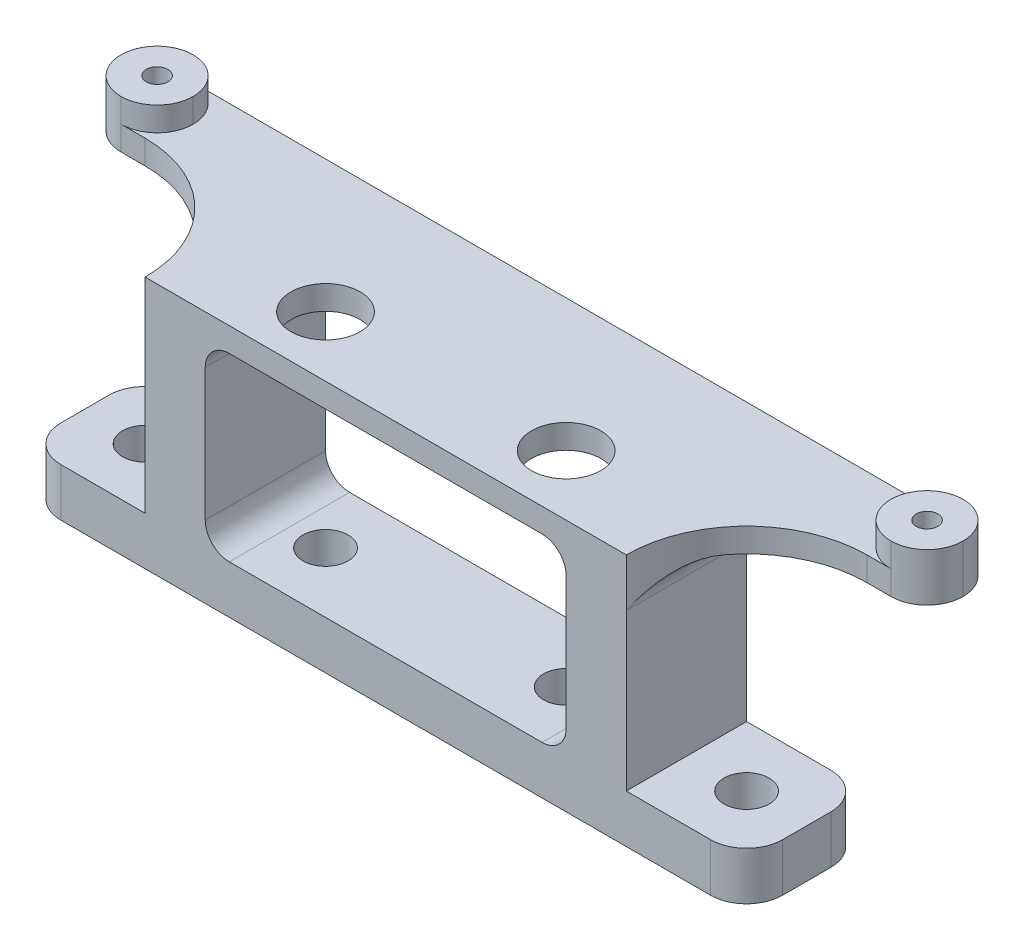
SolidWorks part; units mm, degrees
ref_plane "Front Plane" through (0, 0, 0) normal (0, 0, 1) x (1, 0, 0)
ref_plane "Top Plane" through (0, 0, 0) normal (0, 1, 0) x (1, 0, 0)
ref_plane "Right Plane" through (0, 0, 0) normal (1, 0, 0) x (0, 0, -1)
sketch "Sketch1" plane through (0, 0, 0) normal (0, 1, 0) x (1, 0, 0)
  line L1 (-30, -5) -> (30, -5)
  line L2 (-30, -5) -> (-30, 5)
  line L3 (-30, 5) -> (30, 5)
  line L4 (30, -5) -> (30, 5)
  line L5 (-30, -5) -> (30, 5) construction
  line L6 (-30, 5) -> (30, -5) construction
  point P0 (0, 0)
  dimension "D1" = 60
  dimension "D2" = 10
extrude "Boss-Extrude1" add sketch "Sketch1" along normal blind 4 contours L2 L3 L4 L1
sketch "Sketch2" plane through (0, 4, 0) normal (0, 1, 0) x (1, 0, 0)
  line L0 (0, 0) -> (50000, 0) construction
  line L1 (0, 0) -> (0, 50000) construction
  circle A0 centre (-25, 0) radius 1.875
  circle A1 centre (-10, 0) radius 1.875
  circle A2 centre (10, 0) radius 1.875
  circle A3 centre (25, 0) radius 1.875
  dimension "D5" = 3.75
  dimension "D1" = 10
  dimension "D2" = 10
  dimension "D3" = 25
  dimension "D4" = 25
extrude "Cut-Extrude1" cut sketch "Sketch2" against normal through all
sketch "Sketch4" plane through (0, 4, 0) normal (0, 1, 0) x (1, 0, 0)
  line L0 (-23.125, 0) -> (-11.875, 0) construction
  line L1 (11.875, 0) -> (23.125, 0) construction
  line L2 (-30, 5) -> (30, 5) construction
  line L3 (-20, -5) -> (-15, -5)
  line L4 (-20, -5) -> (-20, 5)
  line L5 (-20, 5) -> (-15, 5)
  line L6 (-15, -5) -> (-15, 5)
  line L7 (-20, -5) -> (-15, 5) construction
  line L8 (-20, 5) -> (-15, -5) construction
  line L16 (15, -5) -> (20, -5)
  line L17 (15, -5) -> (15, 5)
  line L18 (15, 5) -> (20, 5)
  line L19 (20, -5) -> (20, 5)
  line L20 (15, -5) -> (20, 5) construction
  line L21 (15, 5) -> (20, -5) construction
  circle A0 centre (-25, 0) radius 1.875 construction
  circle A1 centre (-10, 0) radius 1.875 construction
  circle A2 centre (10, 0) radius 1.875 construction
  circle A3 centre (25, 0) radius 1.875 construction
  point P14 (-17.5, 0)
  point P27 (17.5, 0)
  dimension "D1" = 5
extrude "Boss-Extrude2" add sketch "Sketch4" along normal blind 15
sketch "Sketch5" plane through (0, 19, 0) normal (0, 1, 0) x (1, 0, 0)
  line L0 (-20, -5) -> (20, -5)
  line L1 (20, -5) -> (20, 5)
  line L2 (20, 5) -> (35, 5)
  line L3 (35, 5) -> (35, 11)
  line L4 (35, 11) -> (-35, 11)
  line L5 (-35, 11) -> (-35, 5)
  line L6 (-35, 5) -> (-20, 5)
  line L7 (-20, 5) -> (-20, -5)
  dimension "D1" = 70
  dimension "D2" = 6
extrude "Boss-Extrude3" add sketch "Sketch5" along normal blind 4
sketch "Sketch7" plane through (0, 23, 0) normal (0, 1, 0) x (1, 0, 0)
  line L0 (-20, 5) -> (20, 5) construction
  line L1 (0, 5) -> (0, 11) construction
  line L2 (20, 5) -> (35, 5) construction
  line L3 (-29, 11) -> (29, 11)
  line L4 (-29, 11) -> (-29, 5)
  line L5 (-29, 5) -> (29, 5)
  line L6 (29, 11) -> (29, 5)
  line L7 (-29, 11) -> (29, 5) construction
  line L8 (-29, 5) -> (29, 11) construction
  line L9 (35, 11) -> (-35, 11) construction
  point P7 (0, 8)
  point P14 (0, 11)
  dimension "D1" = 58
sketch "Sketch8" plane through (0, 23, 0) normal (0, 1, 0) x (1, 0, 0)
  line L0 (-32, 8) -> (32, 8) construction
  circle A0 centre (32, 8) radius 0.9
  circle A1 centre (-32, 8) radius 0.9
  point P4 (0, 8)
  dimension "D1" = 1.8
  dimension "D2" = 64
extrude "Cut-Extrude2" cut sketch "Sketch7" against normal blind 2
sketch "Sketch9" plane through (0, 23, 0) normal (0, 1, 0) x (1, 0, 0)
  line L4 (20, 5) -> (-20, 5)
  line L5 (-20, 5) -> (-20, -5)
  line L6 (-20, -5) -> (20, -5)
  line L7 (20, -5) -> (20, 5)
  line L8 (20, 5) -> (-20, 5)
  line L9 (-20, 5) -> (-20, -5)
  line L10 (-20, -5) -> (20, -5)
  line L11 (20, -5) -> (20, 5)
  dimension "D1" = 0
extrude "Cut-Extrude3" cut sketch "Sketch9" against normal up to surface (2 mm away) up to face at (0, 21, -7)
sketch "Sketch10" plane through (0, 21, 0) normal (0, 1, 0) x (1, 0, 0)
  circle A0 centre (10, 0) radius 1.875 construction
  circle A1 centre (-10, 0) radius 1.875 construction
  circle A2 centre (10, 0) radius 1.875 construction
  circle A3 centre (-10, 0) radius 1.875 construction
  circle A4 centre (-10, 0) radius 2.875
  circle A5 centre (10, 0) radius 2.875
  dimension "D1" = 1
extrude "Cut-Extrude5" cut sketch "Sketch10" against normal up to next
fillet "Fillet1" radius 10 2 edges at (20, 20, -5) (-20, 20, -5)
fillet "Fillet2" radius 3 12 edges at (30, 2, -5) (30, 2, 5) (-30, 2, -5) (-30, 2, 5) (-35, 21, -11) (-35, 21, -5) (-29, 22, -11) (29, 22, -11) (35, 21, -11) (35, 21, -5) (-29, 22, -4.9499) (29, 22, -4.9499)
fillet "Fillet3" radius 2 4 edges at (15, 19, 0) (-15, 19, 0) (-15, 4, 0) (15, 4, 0)
extrude "Cut-Extrude4" cut sketch "Sketch8" against normal through all
fillet "Fillet4" radius 2 4 edges at (-16.5, 19, -5) (16.5, 19, -5) (-20, 19, 0) (20, 19, 0)
